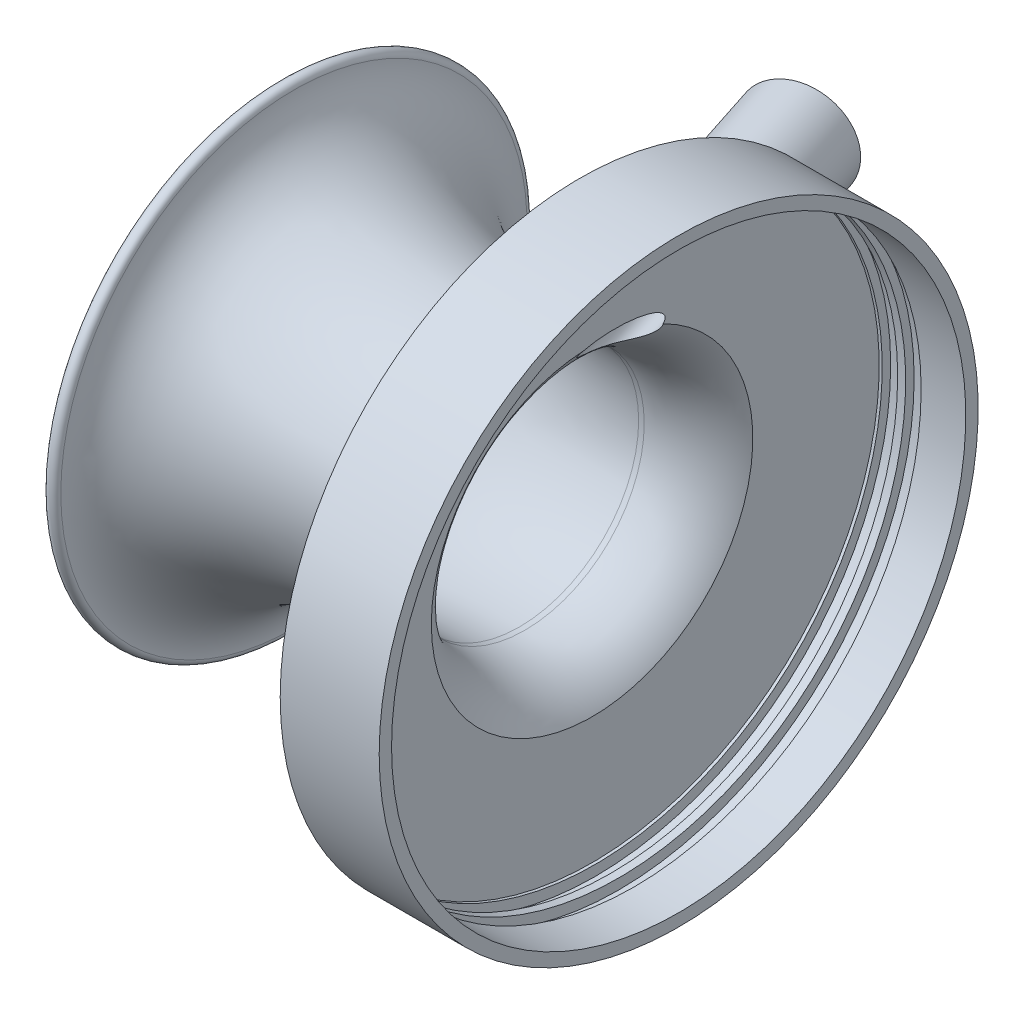
SolidWorks part; units mm, degrees
material "PVC 0.007 Plasticized"
ref_plane "Front Plane" through (0, 0, 0) normal (0, 0, 1) x (1, 0, 0)
ref_plane "Top Plane" through (0, 0, 0) normal (0, 1, 0) x (1, 0, 0)
ref_plane "Right Plane" through (0, 0, 0) normal (1, 0, 0) x (0, 0, -1)
sketch "Sketch1" plane through (0, 0, 0) normal (0, 0, 1) x (1, 0, 0)
  line L0 (-17.78, 33.4033) -> (-17.78, 59.3503)
  line L1 (-34.3222, 33.4033) -> (-9.5791, 33.4033) construction
  line L3 (-34.3222, 0.4033) -> (53.9483, 0.4033) construction
  line L11 (-32.6995, 24.8889) -> (-31.5799, 24.9144)
  line L12 (-17.78, 59.3503) -> (0, 59.3503)
  line L13 (-32.7541, 27.4283) -> (-31.68, 27.4528)
  line L14 (-20.32, 34.1122) -> (-20.32, 61.8903)
  line L15 (-20.32, 61.8903) -> (0, 61.8903)
  line L16 (0, 61.8903) -> (0, 59.3503)
  circle A4 centre (-32.5108, 41.8889) radius 17 construction
  arc A5 (-17.78, 33.4033) -> (-31.5799, 24.9144) centre (-32.5108, 41.8889) cw
  arc A6 (-20.32, 34.1122) -> (-31.68, 27.4528) centre (-32.5108, 41.8889) cw
  arc A7 (-81.5276, 48.209) -> (-78.9882, 48.2636) centre (-80.2579, 48.2363) cw
  ellipse E0 centre (-33.2232, 49.2475) end of major axis (15.0812, 50.2859) minor radius 24.3642 (-81.5276, 48.209) -> (-32.6995, 24.8889) ccw
  ellipse E1 centre (-33.2232, 49.2475) end of major axis (-81.5276, 48.209) minor radius 24.3642 construction
  spline S0 degree 1 poles (-78.9882, 48.2636) (-32.7541, 27.4283) knots 0 0 1 1 construction
  spline S1 degree 3 poles (-78.9882, 48.2636) (-78.9745, 47.627) (-78.8248, 46.3708) (-78.0214, 43.8262) (-76.0087, 40.6014) (-71.877, 36.8457) (-66.142, 33.4811) (-59.043, 30.716) (-50.8772, 28.701) (-42.0017, 27.5355) (-35.8146, 27.3625) (-32.7541, 27.4283) knots 3.141593 3.141593 3.141593 3.141593 3.239767 3.337942 3.534292 3.730641 3.926991 4.12334 4.31969 4.516039 4.712389 4.712389 4.712389 4.712389
  dimension "D3" = 24.3586
  dimension "D1" = 33.0001
  dimension "D2" = 15.4432
  dimension "D4" = 48.3044
  dimension "D5" = 58.947
  dimension "D10" = 34
  dimension "D11" = 17
  dimension "D12" = 31.5799
  dimension "D9" = 1.27
  dimension "D6" = 17.78
  dimension "D8" = 24.4856
  dimension "D7" = 2.54
  dimension "D13" = 31.68
  dimension "D14" = 34.3222
  dimension "D15" = 0.4033
revolve "Revolve1" add sketch "Sketch1" angle 360 about L3
ref_axis "Axis1" through (0, 65.659, 0) along (0, -1, 0)
ref_plane "Plane1" through (0, 0, 0) normal (-0.309, 0, -0.9511) x (0, -1, 0)
ref_plane "Plane2" through (-13.3434, 0, -41.0666) normal (-0.309, 0, -0.9511) x (0, -1, 0)
sketch "Sketch2" plane through (-13.3434, 0, -41.0666) normal (-0.309, 0, -0.9511) x (0, -1, 0)
  line L0 (-33.0001, 18.6255) -> (-26.9006, 18.6255) construction
  circle A0 centre (-30.8893, 15.4505) radius 3.175
  circle A1 centre (-30.8893, 15.4505) radius 10.16
  circle A2 centre (-30.8893, 15.4505) radius 5.5562
  ellipse E0 centre (0, 18.6255) end of major axis (-33.0001, 18.6255) minor radius 9.0224 construction
  dimension "D1" = 6.35
  dimension "D2" = 20.32
  dimension "D3" = 11.1125
  dimension "D4" = 0
extrude "Boss-Extrude1" add sketch "Sketch2" against normal up to next separate body contours A2 A0 region at (-28.0376, 36.2884, -36.2922)
extrude "Cut-Extrude1" cut sketch "Sketch2<3>" along direction (-0.309, 0, -0.9511) on the side against the normal blind 40.64 and the other way through all contours A0 region at (-28.0376, 30.8893, -36.2922)
sketch "Sketch2<3>" plane through (-13.3434, 0, -41.0666) normal (-0.309, 0, -0.9511) x (0, -1, 0) same geometry as "Sketch2"
extrude "Boss-Extrude3" add sketch "Sketch2<4>" against normal blind 1.016 and the other way blind 25.4 contours A1 A2 region at (-28.0376, 40.7619, -36.2922)
sketch "Sketch2<4>" plane through (-13.3434, 0, -41.0666) normal (-0.309, 0, -0.9511) x (0, -1, 0) same geometry as "Sketch2"
sketch "Sketch5" plane through (0, 0, 0) normal (0, 0, 1) x (1, 0, 0)
  line L0 (-13.9854, 60.6838) -> (-17.1604, 60.6838)
  line L1 (-13.9854, 60.6838) -> (-13.9854, 59.0963)
  line L2 (-17.1604, 60.6838) -> (-17.1604, 59.0963)
  line L4 (0, 0) -> (-88.0301, 0) construction
  line L5 (-17.1604, 59.0963) -> (-17.1604, 57.8263)
  line L7 (-13.9854, 57.8263) -> (-13.9854, 59.0963)
  line L14 (-17.1604, 57.8263) -> (-13.9854, 57.8263)
  line L15 (-9.1671, 60.6838) -> (-12.3421, 60.6838)
  line L16 (-9.1671, 60.6838) -> (-9.1671, 59.0963)
  line L17 (-12.3421, 60.6838) -> (-12.3421, 59.0963)
  line L18 (-12.3421, 59.0963) -> (-12.3421, 57.8263)
  line L19 (-9.1671, 57.8263) -> (-9.1671, 59.0963)
  line L20 (-12.3421, 57.8263) -> (-9.1671, 57.8263)
  line L21 (-20.32, 61.8903) -> (-20.32, -61.0838) construction
  line L22 (-20.32, 61.8903) -> (-20.32, -61.0838)
  dimension "D1" = 1.5875
  dimension "D2" = 59.0963
  dimension "D3" = 3.175
  dimension "D4" = 0
  dimension "D5" = 13.9854
  dimension "D6" = 1.27
  dimension "D8" = 1.5875
  dimension "D9" = 3.175
  dimension "D11" = 9.1671
revolve "Cut-Revolve2" cut sketch "Sketch5" angle 360 about L4 region at (-15.5729, 59.2551, 0) region at (-10.7546, 59.2551, 0)
